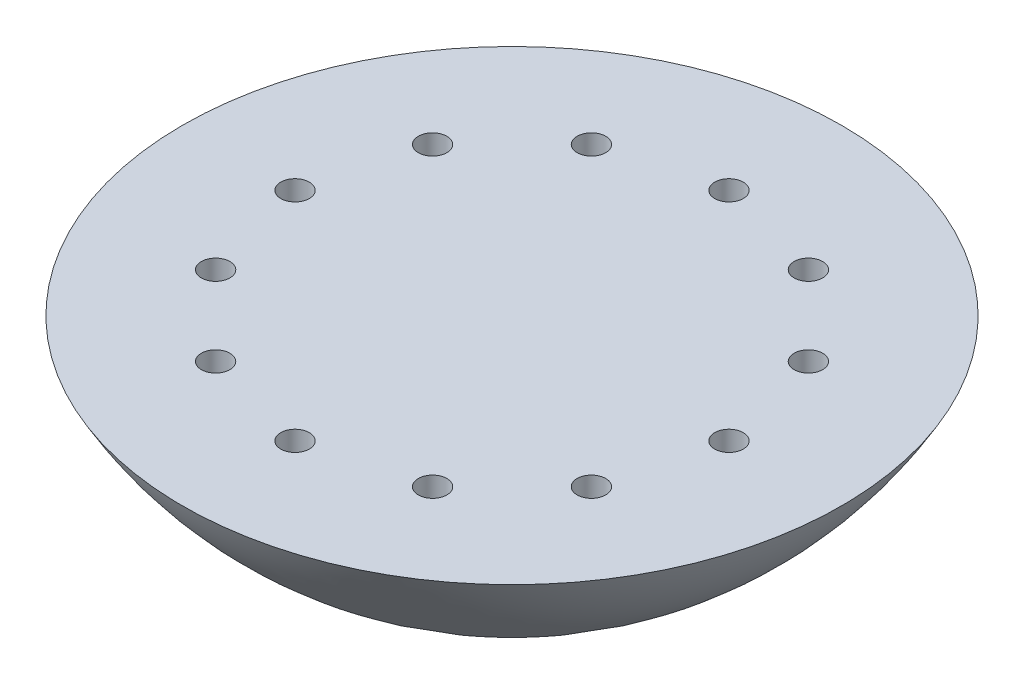
SolidWorks part; units mm, degrees
ref_plane "Front Plane" through (0, 0, 0) normal (0, 0, 1) x (1, 0, 0)
ref_plane "Top Plane" through (0, 0, 0) normal (0, 1, 0) x (1, 0, 0)
ref_plane "Right Plane" through (0, 0, 0) normal (1, 0, 0) x (0, 0, -1)
sketch "Main Revolve Sketch" plane through (0, 0, 0) normal (0, 0, 1) x (1, 0, 0)
  line L0 (0, 0) -> (0, 96.25) construction
  line L3 (-82.5, 13.75) -> (-82.5, 0) construction
  line L4 (-82.5, 0) -> (-82.5, -13.75) construction
  line L8 (0, 96.25) -> (96.25, 96.25) construction
  line L9 (0, -96.25) -> (96.25, -96.25) construction
  line L11 (0, 0) -> (0, -96.25) construction
  line L14 (0, -53.75) -> (-72.1543, -53.75)
  line L16 (0, -53.75) -> (0, -96.25)
  arc A0 (0, 96.25) -> (-82.5, 13.75) centre (0, 13.75) ccw construction
  arc A1 (-72.1543, -53.75) -> (0, -96.25) centre (0, -13.75) ccw
  dimension "D1" = 82.5
  dimension "D2" = 27.5
  dimension "D3" = 53.75
revolve "Main Revolve" add sketch "Main Revolve Sketch" angle 360 about L0
sketch "Sketch5" plane through (0, 0, 0) normal (0, 1, 0) x (1, 0, 0)
  line L8 (0, 0) -> (0, -47.5) construction
  line L9 (-23.75, 41.1362) -> (0, 47.5) construction
  line L10 (47.5, 0) -> (0, 0) construction
  line L11 (0, 0) -> (41.1362, 23.75) construction
  line L12 (41.1362, 23.75) -> (23.75, 41.1362) construction
  line L13 (23.75, 41.1362) -> (0, 0) construction
  line L14 (0, 0) -> (0, 47.5) construction
  line L15 (0, 47.5) -> (23.75, 41.1362) construction
  line L16 (-23.75, 41.1362) -> (0, 0) construction
  line L17 (0, 0) -> (-41.1362, 23.75) construction
  line L18 (-41.1362, 23.75) -> (-47.5, 0) construction
  line L19 (-47.5, 0) -> (0, 0) construction
  line L20 (0, 0) -> (-41.1362, -23.75) construction
  line L21 (47.5, 0) -> (41.1362, 23.75) construction
  line L22 (-23.75, 41.1362) -> (-41.1362, 23.75) construction
  line L23 (-41.1362, -23.75) -> (-47.5, 0) construction
  line L24 (0, 0) -> (-23.75, -41.1362) construction
  line L25 (0, 0) -> (41.1362, -23.75) construction
  line L26 (-23.75, -41.1362) -> (-41.1362, -23.75) construction
  line L29 (41.1362, -23.75) -> (47.5, 0) construction
  line L30 (-23.75, -41.1362) -> (0, -47.5) construction
  line L31 (0, -47.5) -> (23.75, -41.1362) construction
  line L32 (23.75, -41.1362) -> (41.1362, -23.75) construction
  line L33 (0, 0) -> (23.75, -41.1362) construction
  circle A8 centre (0, 0) radius 40 construction
  circle A9 centre (0, -47.5) radius 3.125
  circle A10 centre (47.5, 0) radius 3.125
  circle A11 centre (41.1362, 23.75) radius 3.125
  circle A12 centre (23.75, 41.1362) radius 3.125
  circle A13 centre (0, 47.5) radius 3.125
  circle A14 centre (-23.75, 41.1362) radius 3.125
  circle A15 centre (-41.1362, 23.75) radius 3.125
  circle A16 centre (-47.5, 0) radius 3.125
  circle A17 centre (-41.1362, -23.75) radius 3.125
  circle A18 centre (41.1362, -23.75) radius 3.125
  circle A19 centre (-23.75, -41.1362) radius 3.125
  circle A20 centre (23.75, -41.1362) radius 3.125
  circle A21 centre (0, 47.5) radius 5
  circle A22 centre (23.75, 41.1362) radius 5
  circle A23 centre (41.1362, 23.75) radius 5
  circle A24 centre (47.5, 0) radius 5
  circle A25 centre (41.1362, -23.75) radius 5
  circle A26 centre (23.75, -41.1362) radius 5
  circle A27 centre (0, -47.5) radius 5
  circle A28 centre (-23.75, -41.1362) radius 5
  circle A29 centre (-41.1362, -23.75) radius 5
  circle A30 centre (-47.5, 0) radius 5
  circle A31 centre (-41.1362, 23.75) radius 5
  circle A32 centre (-23.75, 41.1362) radius 5
  dimension "D1" = 80
  dimension "D3" = 6.25
  dimension "D4" = 10
  dimension "D2" = 47.5
extrude "Cut-Extrude3" cut sketch "Sketch5" against normal through all contours A14 | A13 | A12 | A11 | A10 | A18 | A20 | A9 | A19 | A17 | A16 | A15
extrude "Cut-Extrude4" cut sketch "Sketch5<4>" along normal offset from surface (433.75 mm away) 12.5 from offset 500 up to face at (-41.1362, -53.75, -26.875) offset against normal yes
sketch "Sketch5<4>" plane through (0, 0, 0) normal (0, 1, 0) x (1, 0, 0) same geometry as "Sketch5"
